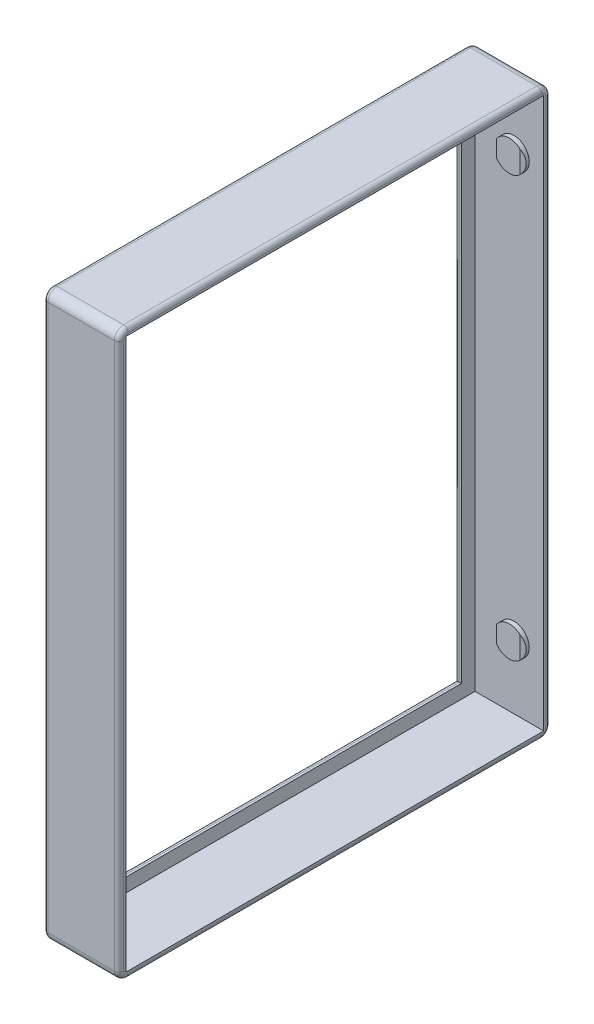
SolidWorks part; units mm, degrees
ref_plane "Front Plane" through (0, 0, 0) normal (0, 0, 1) x (1, 0, 0)
ref_plane "Top Plane" through (0, 0, 0) normal (0, 1, 0) x (1, 0, 0)
ref_plane "Right Plane" through (0, 0, 0) normal (1, 0, 0) x (0, 0, -1)
sketch "Sketch1" plane through (3.3486, 0, 0) normal (-1, 0, 0) x (0, 0, 1)
  line L0 (-28.4017, -129.0389) -> (56.9983, -129.0389)
  line L1 (56.9983, -129.0389) -> (56.9983, -14.6389)
  line L2 (56.9983, -14.6389) -> (-28.4017, -14.6389)
  line L3 (-28.4017, -14.6389) -> (-28.4017, -129.0389)
  line L4 (61.4983, -133.5389) -> (61.4983, -10.1389)
  line L5 (61.4983, -10.1389) -> (-32.9017, -10.1389)
  line L6 (-32.9017, -10.1389) -> (-32.9017, -133.5389)
  line L7 (-32.9017, -133.5389) -> (61.4983, -133.5389)
  line L8 (59.9983, -11.6389) -> (-31.4017, -11.6389)
  line L10 (59.9983, -11.6389) -> (-31.4017, -11.6389)
  line L1256 (-31.4017, -11.6389) -> (-31.4017, -132.0389)
  line L1258 (-31.4017, -11.6389) -> (-31.4017, -132.0389)
  line L1268 (-31.4017, -132.0389) -> (59.9983, -132.0389)
  line L1269 (-31.4017, -132.0389) -> (59.9983, -132.0389)
  line L1270 (59.9983, -132.0389) -> (59.9983, -11.6389)
  line L1271 (59.9983, -132.0389) -> (59.9983, -11.6389)
  dimension "D1" = 0.2
extrude "Boss-Extrude1" add sketch "Sketch1" along normal blind 1.5 contours L6 L7 L4 L5 L1271 L1269 L1258 L10 | L1269 L1271 L10 L1258 L3 L2 L1 L0 region at (3.3486, -133.3835, 14.2983) region at (3.3486, -71.8389, 58.4867)
extrude "Boss-Extrude2" add sketch "Sketch1<3>" against normal blind 15 contours L6 L7 L4 L5 L1271 L1269 L1258 L10 region at (3.3486, -133.3835, 14.2983)
sketch "Sketch1<3>" plane through (3.3486, 0, 0) normal (-1, 0, 0) x (0, 0, 1) same geometry as "Sketch1"
fillet "Fillet1" radius 2 4 edges at (10.0986, -10.1389, -32.9017) (10.0986, -133.5389, -32.9017) (10.0986, -10.1389, 61.4983) (10.0986, -133.5389, 61.4983)
fillet "Fillet2" radius 1 12 edges at (1.8486, -129.0389, 14.2983) (1.8486, -71.8389, 56.9983) (1.8486, -14.6389, 14.2983) (1.8486, -71.8389, -28.4017) (1.8486, -10.7247, 60.9125) (1.8486, -71.8389, 61.4983) (1.8486, -132.9531, 60.9125) (1.8486, -133.5389, 14.2983) (1.8486, -132.9531, -32.3159) (1.8486, -71.8389, -32.9017) (1.8486, -10.7247, -32.3159) (1.8486, -10.1389, 14.2983)
fillet "Fillet5" radius 1 8 edges at (18.3486, -10.7247, -32.3159) (18.3486, -10.1389, 14.2983) (18.3486, -10.7247, 60.9125) (18.3486, -71.8389, 61.4983) (18.3486, -132.9531, 60.9125) (18.3486, -133.5389, 14.2983) (18.3486, -132.9531, -32.3159) (18.3486, -71.8389, -32.9017)
sketch "Sketch3" plane through (0, 0, 59.9983) normal (0, 0, -1) x (-1, 0, 0)
  line L0 (-8.992, -24.0889) -> (-8.992, -27.5889)
  line L1 (-8.992, -116.0889) -> (-8.992, -119.5889)
  circle A0 centre (-11.8486, -117.8389) radius 3.5 construction
  circle A1 centre (-11.8486, -25.8389) radius 3.5 construction
  circle A2 centre (-11.8486, -117.8389) radius 3.5 construction
  circle A3 centre (-11.8486, -25.8389) radius 3.5 construction
  circle A4 centre (-11.8486, -25.8389) radius 3.35
  circle A5 centre (-11.8486, -117.8389) radius 3.35
  dimension "D2" = 3.5
  dimension "D3" = 3.5
  dimension "D1" = 0.15
extrude "Boss-Extrude3" add sketch "Sketch3" along normal blind 1 contours L1 A5 | L0 A4 region at (11.9534, -25.8389, 59.9983) region at (11.9534, -117.8389, 59.9983)
extrude "Boss-Extrude4" add sketch "Sketch3<3>" against normal blind 1 from surface contours L1 A5 | L0 A4 region at (11.9534, -25.8389, 59.9983) region at (11.9534, -117.8389, 59.9983) starting at face at (10.8486, -71.8389, -31.4017)
sketch "Sketch3<3>" plane through (0, 0, 59.9983) normal (0, 0, -1) x (-1, 0, 0) same geometry as "Sketch3"
sketch "Sketch5" plane through (0, -132.0389, 0) normal (0, 1, 0) x (1, 0, 0)
  line L0 (17.1986, 31.4017) -> (14.1986, 30.4017)
  line L1 (18.3486, 31.4017) -> (3.3486, 31.4017) construction
  line L2 (15.1986, 30.4017) -> (8.992, 30.4017) construction
  line L3 (15.1986, 30.4017) -> (8.992, 30.4017) construction
  line L4 (14.1986, 30.4017) -> (17.1986, 30.4017)
  line L5 (17.1986, 30.4017) -> (17.1986, 31.4017)
  line L6 (15.1986, -58.9983) -> (8.992, -58.9983) construction
  line L7 (15.1986, -58.9983) -> (8.992, -58.9983) construction
  line L8 (17.1986, -59.9983) -> (14.1986, -58.9983)
  line L9 (18.3486, -59.9983) -> (3.3486, -59.9983) construction
  line L10 (14.1986, -58.9983) -> (17.1986, -58.9983)
  line L11 (17.1986, -58.9983) -> (17.1986, -59.9983)
  dimension "D1" = 2
  dimension "D2" = 1
  dimension "D3" = 2
  dimension "D4" = 1
extrude "Cut-Extrude1" cut sketch "Sketch5" along normal up to surface (120.4 mm away) up to face at (10.8486, -11.6389, 14.2983)
